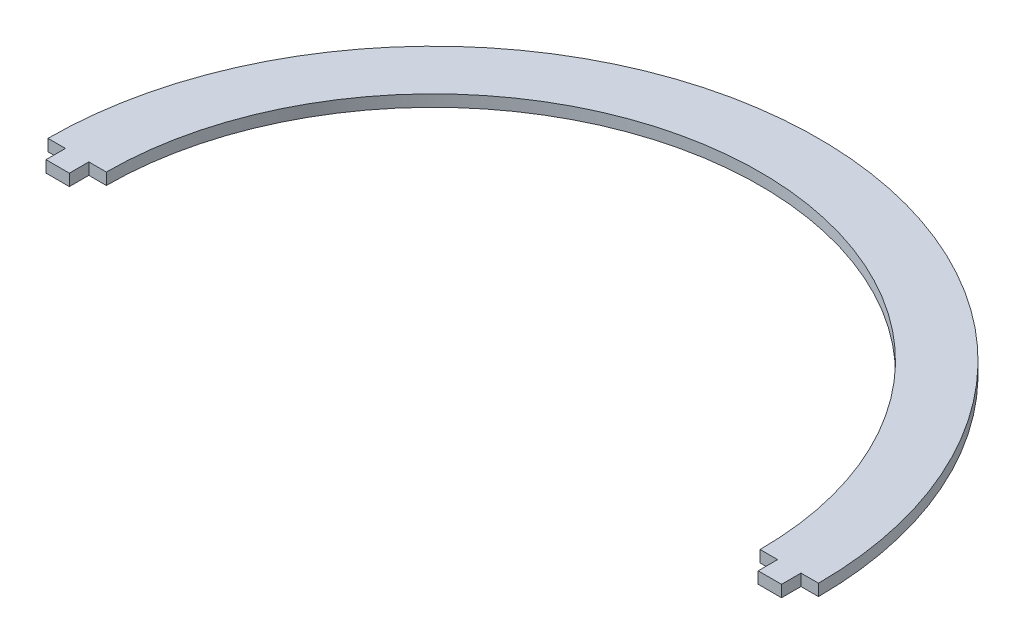
SolidWorks part; units mm, degrees
ref_plane "Front Plane" through (0, 0, 0) normal (0, 0, 1) x (1, 0, 0)
ref_plane "Top Plane" through (0, 0, 0) normal (0, 1, 0) x (1, 0, 0)
ref_plane "Right Plane" through (0, 0, 0) normal (1, 0, 0) x (0, 0, -1)
sketch "Sketch1" plane through (0, 0, 0) normal (0, 1, 0) x (1, 0, 0)
  line L0 (-94.5, 0) -> (-88.5, 0)
  line L1 (-88.5, 0) -> (-88.5, 5)
  line L2 (-88.5, 5) -> (-84, 5)
  line L3 (84, 5) -> (88.5, 5)
  line L4 (88.5, 5) -> (88.5, 0)
  line L5 (88.5, 0) -> (94.5, 0)
  line L6 (94.5, 0) -> (94.5, 5)
  line L7 (94.5, 5) -> (99, 5)
  line L8 (-99, 5) -> (-94.5, 5)
  line L9 (-94.5, 5) -> (-94.5, 0)
  arc A0 (-84, 5) -> (84, 5) centre (0, 5) cw
  arc A1 (99, 5) -> (-99, 5) centre (0, 5) ccw
  point P12 (3.2976, 8.7566)
  point P14 (23.6261, 5.9332)
  point P16 (9.9326, 4.8039)
  point P17 (10.7796, 6.3568)
  point P18 (0, 7.4861)
  dimension "D1" = 6
  dimension "D2" = 15
  dimension "D3" = 5
  dimension "D4" = 177
extrude "Boss-Extrude1" add sketch "Sketch1" along normal mid plane 3
